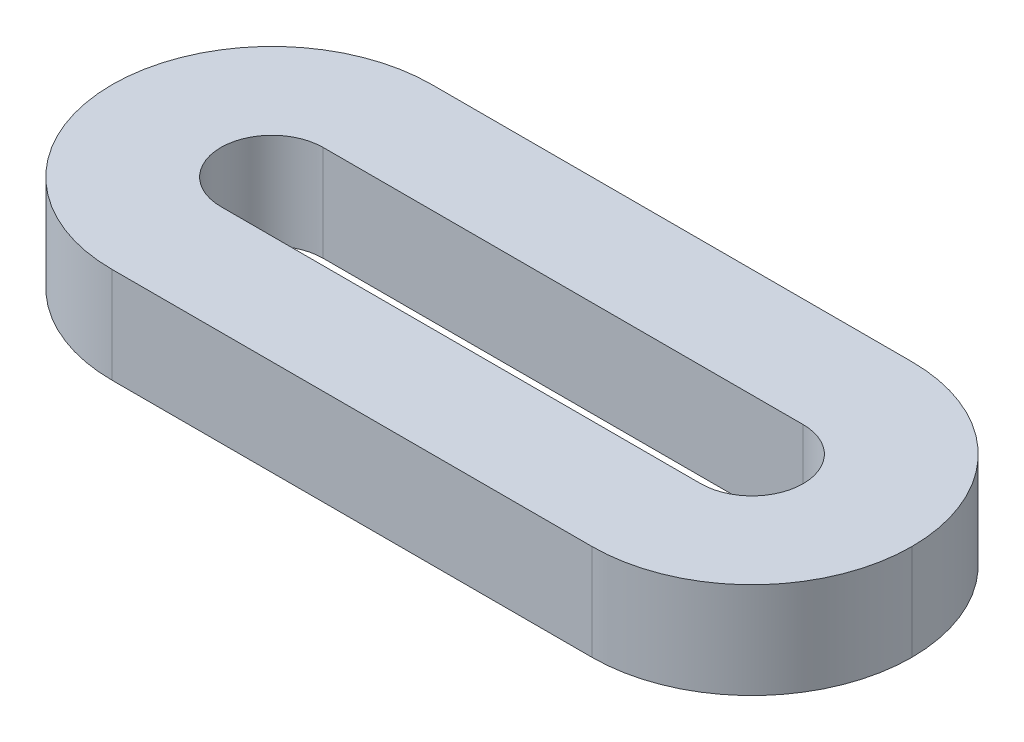
SolidWorks part; units mm, degrees
ref_plane "前视基准面" through (0, 0, 0) normal (0, 0, 1) x (1, 0, 0)
ref_plane "上视基准面" through (0, 0, 0) normal (0, 1, 0) x (1, 0, 0)
ref_plane "右视基准面" through (0, 0, 0) normal (1, 0, 0) x (0, 0, -1)
other "Configuration Table"
sketch "草图1" plane through (0, 0, 0) normal (0, 1, 0) x (1, 0, 0)
  line L0 (0, 0) -> (-15, 0) construction
  line L1 (0, -1.6) -> (-15, -1.6)
  line L2 (0, 1.6) -> (-15, 1.6)
  line L4 (-20, 5) -> (5, 5)
  line L5 (-20, 5) -> (-20, -5)
  line L6 (-20, -5) -> (5, -5)
  line L7 (5, 5) -> (5, -5)
  arc A0 (0, -1.6) -> (0, 1.6) centre (0, 0) ccw
  arc A1 (-15, 1.6) -> (-15, -1.6) centre (-15, 0) ccw
  point P3 (-7.5, 0)
  point P14 (12.7455, 2.6801)
  dimension "D1" = 1.6
  dimension "D2" = 15
  dimension "D3" = 5
  dimension "D4" = 5
  dimension "D5" = 5
extrude "凸台-拉伸1" add sketch "草图1" along normal blind 3
fillet "圆角1" radius 5 4 edges at (5, 1.5, 5) (5, 1.5, -5) (-20, 1.5, -5) (-20, 1.5, 5)
